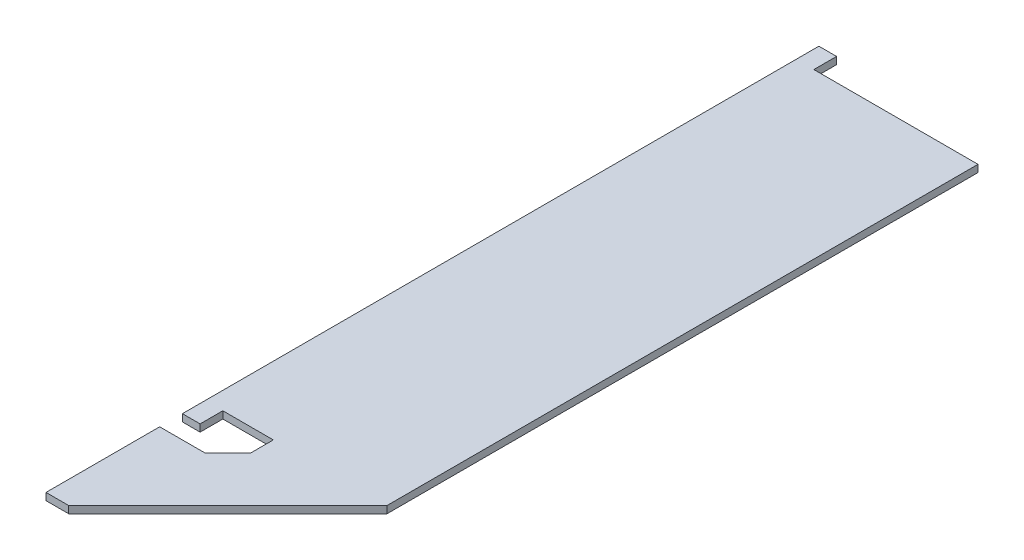
SolidWorks part; units mm, degrees
ref_plane "Front Plane" through (0, 0, 0) normal (0, 0, 1) x (1, 0, 0)
ref_plane "Top Plane" through (0, 0, 0) normal (0, 1, 0) x (1, 0, 0)
ref_plane "Right Plane" through (0, 0, 0) normal (1, 0, 0) x (0, 0, -1)
sketch "Sketch1" plane through (0, 0, 0) normal (0, 1, 0) x (1, 0, 0)
  line L0 (-3.175, -41.275) -> (-3.175, -47.625)
  line L1 (-12.7, -41.275) -> (-3.175, -41.275)
  line L2 (-12.7, -41.275) -> (-12.7, 41.275)
  line L3 (-12.7, 41.275) -> (12.7, 41.275)
  line L4 (12.7, -41.275) -> (12.7, 41.275)
  line L5 (-12.7, -41.275) -> (12.7, 41.275) construction
  line L6 (-12.7, 41.275) -> (12.7, -41.275) construction
  line L7 (-3.175, -47.625) -> (-12.7, -47.625)
  line L8 (-12.7, -47.625) -> (-12.7, -63.5)
  line L9 (-12.7, -63.5) -> (12.7, -63.5)
  line L10 (12.7, -63.5) -> (12.7, -41.275)
  point P0 (0, 0)
  dimension "D1" = 25.4
  dimension "D2" = 82.55
  dimension "D3" = 15.875
  dimension "D4" = 6.35
  dimension "D5" = 15.875
extrude "Boss-Extrude1" add sketch "Sketch1" along normal blind 1.0008
sketch "Sketch2" plane through (0, 0, 41.275) normal (0, 0, 1) x (1, 0, 0)
  line L0 (-12.7, 1.0008) -> (-3.175, 1.0008) construction
  line L1 (-12.7, 0) -> (-10.2279, 0)
  line L2 (-12.7, 0) -> (-12.7, 1.0008)
  line L3 (-12.7, 1.0008) -> (-10.2279, 1.0008)
  line L4 (-10.2279, 0) -> (-10.2279, 1.0008)
  dimension "D1" = 2.667
extrude "Boss-Extrude2" add sketch "Sketch2" along normal blind 3.175
mirror "Mirror1" about plane through (0, 0, 0) normal (0, 0, 1) of "Boss-Extrude2"
chamfer "Chamfer2" distance 22.225 angle 45 1 edges at (12.7, 0.5004, 63.5)
chamfer "Chamfer3" distance 3.175 angle 45 1 edges at (-3.175, 0.5004, 47.625)
equation "\"looseTol\"= 0.02in"
equation "\"tightTol\"= 0.005in"
equation "\"normTol\"= 0.01in"
equation "\"D1@Sketch2\"=0.125000in-\"looseTol\""
